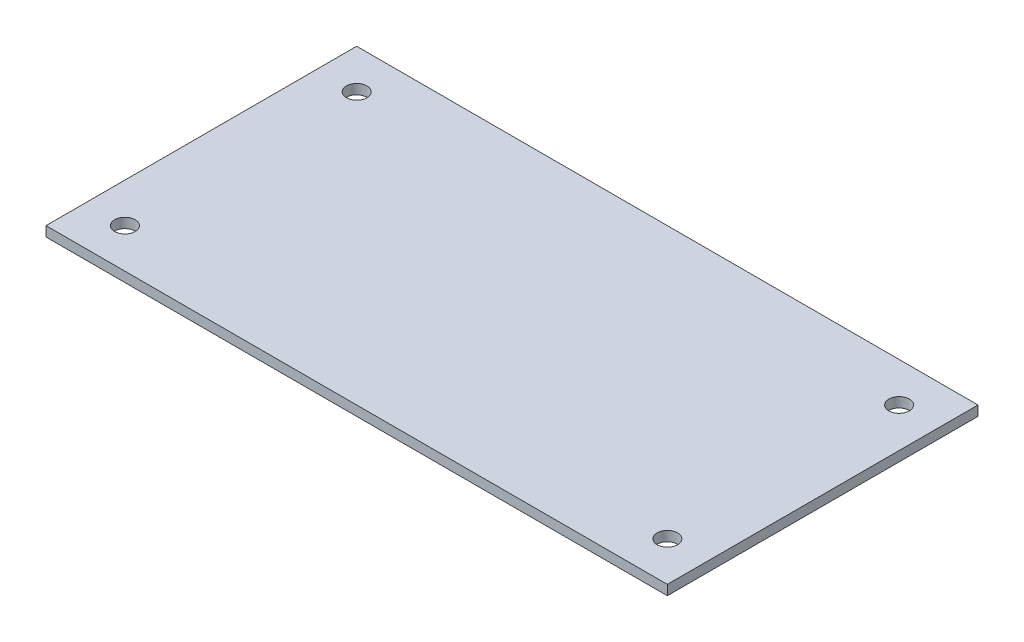
SolidWorks part; units mm, degrees
note: The reader was unsure of these and kept them because the rebuilt part matched: thickness of "Base-Flange1", "Sheet-Metal1", "Sheet-Metal2".
ref_plane "Front" through (0, 0, 0) normal (0, 0, 1) x (1, 0, 0)
ref_plane "Top" through (0, 0, 0) normal (0, 1, 0) x (1, 0, 0)
ref_plane "Right" through (0, 0, 0) normal (1, 0, 0) x (0, 0, -1)
sketch "Sketch2"
  line L1 (-100, -50) -> (100, -50)
  line L2 (-100, -50) -> (-100, 50)
  line L3 (-100, 50) -> (100, 50)
  line L4 (100, -50) -> (100, 50)
  line L5 (-100, -50) -> (100, 50) construction
  line L6 (-100, 50) -> (100, -50) construction
  point P0 (0, 0)
  dimension "D1" = 200
  dimension "D2" = 100
base flange "Base-Flange1" sketch "Sketch2" thickness 3.175 reverse thickness direction no parameters "D1"=0.7366
hole_wizard "M6 Clearance Hole1" positions "Sketch7" profile "Sketch8" hole size "M6" standard "ANSI Metric"
sketch "Sketch7" plane through (0, 0, 0) normal (0, 1, 0) x (1, 0, 0)
  line L0 (-87.3, 37.3) -> (87.3, -37.3) construction
  line L2 (87.3, 37.3) -> (-87.3, -37.3) construction
  line L4 (87.3, 37.3) -> (87.3, -37.3) construction
  line L6 (0, 0) -> (87.3, 0) construction
  line L8 (100, 50) -> (-100, 50) construction
  line L10 (100, -50) -> (100, 50) construction
  point P0 (-87.3, -37.3)
  point P2 (-87.3, 37.3)
  point P4 (87.3, 37.3)
  point P6 (87.3, -37.3)
  dimension "D1" = 12.7
  dimension "D2" = 12.7
sketch "Sketch8" plane through (-87.3, 0, 37.3) normal (1, 0, 0) x (0, 0, 1)
  line L0 (0, 0) -> (0, 20.7328)
  line L1 (0, 20.7328) -> (3.3, 18.75)
  line L2 (3.3, 18.75) -> (3.3, 0)
  line L5 (3.3, 0) -> (0, 0)
  line L10 (0, 20.7328) -> (-3.3, 18.75) construction
  line L11 (0, -6.35) -> (0, 107.95) construction
  dimension "Hole Dia." = 6.6
  dimension "Hole Depth" = 18.75
  dimension "Drill Angle" = 118
sketch "Bend-Lines1" [suppressed] plane through (0, 0, 0) normal (0, 1, 0) x (1, 0, 0)
sketch "Bounding-Box1" [suppressed] plane through (0, 0, 0) normal (0, 1, 0) x (1, 0, 0)
sheet metal parameters "Sheet-Metal1" thickness 3.175 parameters "D1"=0.7366, "D7"=0.7366
flat pattern "Flat-Pattern1" [suppressed]
sketch "Bend-Lines2" plane through (0, 0, 0) normal (0, 1, 0) x (1, 0, 0)
sketch3d "Bounding-Box2" [suppressed]
  line L0 (-152.4, -152.4, 0) -> (-152.4, 152.4, 0) construction
  line L1 (152.4, -152.4, 0) -> (152.4, 152.4, 0) construction
  line L2 (-152.4, -152.4, 0) -> (152.4, -152.4, 0) construction
  line L3 (-152.4, 152.4, 0) -> (152.4, 152.4, 0) construction
sheet metal parameters "Sheet-Metal2" thickness 3.175 parameters "D1"=0.7366, "D7"=0.7366
flat pattern "Flat-Pattern1"
sketch "Bend-Lines2" plane through (0, 0, 0) normal (0, 1, 0) x (1, 0, 0)
sketch3d "Bounding-Box2" [suppressed]
  line L0 (100, 50, 0) -> (-100, 50, 0) construction
  line L1 (100, -50, 0) -> (-100, -50, 0) construction
  line L2 (100, 50, 0) -> (100, -50, 0) construction
  line L3 (-100, 50, 0) -> (-100, -50, 0) construction
